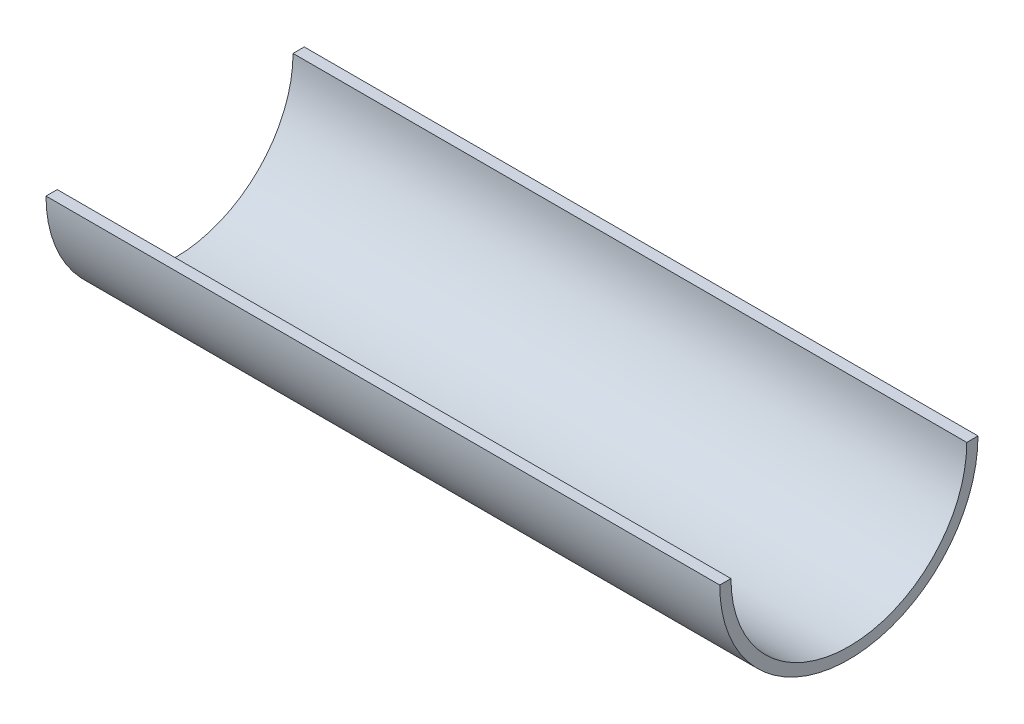
SolidWorks part; units mm, degrees
ref_plane "Front Plane" through (0, 0, 0) normal (0, 0, 1) x (1, 0, 0)
ref_plane "Top Plane" through (0, 0, 0) normal (0, 1, 0) x (1, 0, 0)
ref_plane "Right Plane" through (0, 0, 0) normal (1, 0, 0) x (0, 0, -1)
sketch "Sketch1" plane through (0, 0, 0) normal (1, 0, 0) x (0, 0, -1)
  line L0 (21, 0) -> (23, 0)
  line L5 (-23, 0) -> (-21, 0)
  arc A0 (21, 0) -> (-21, 0) centre (0, 0) cw
  arc A1 (23, 0) -> (-23, 0) centre (0, 0) cw
  dimension "D3" = 21
  dimension "D1" = 2
extrude "Boss-Extrude1" add sketch "Sketch1" along normal blind 120
